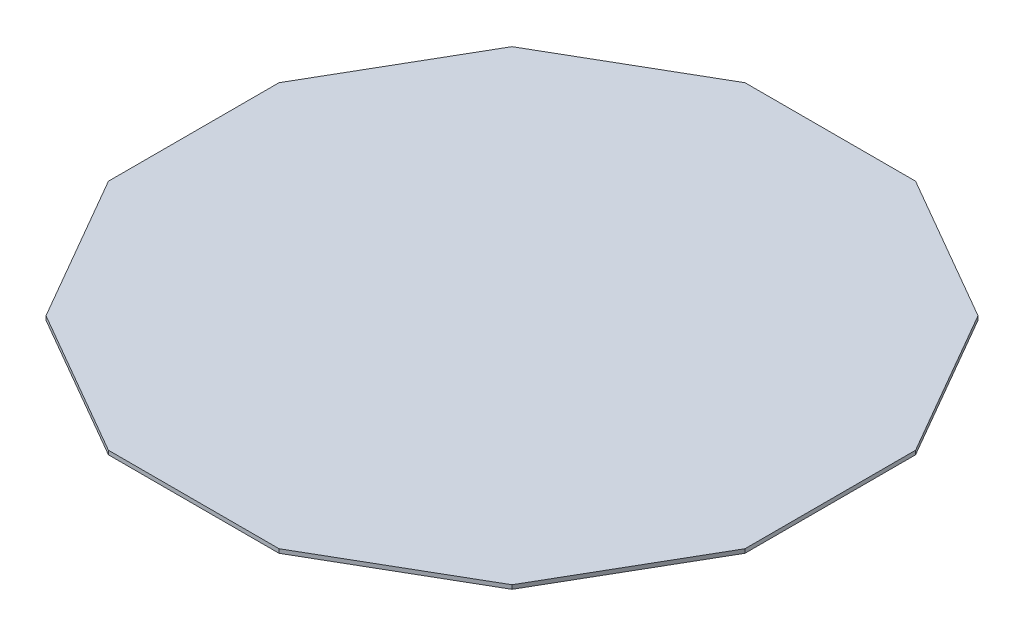
SolidWorks part; units mm, degrees
ref_plane "正面" through (0, 0, 0) normal (0, 0, 1) x (1, 0, 0)
ref_plane "平面" through (0, 0, 0) normal (0, 1, 0) x (1, 0, 0)
ref_plane "右側面" through (0, 0, 0) normal (1, 0, 0) x (0, 0, -1)
sketch "ｽｹｯﾁ1" plane through (0, 0, 0) normal (0, 1, 0) x (1, 0, 0)
  line L0 (-80, -21.4359) -> (-58.5641, -58.5641)
  line L1 (80, 21.4359) -> (58.5641, 58.5641)
  line L2 (58.5641, 58.5641) -> (21.4359, 80)
  line L3 (21.4359, 80) -> (-21.4359, 80)
  line L4 (-21.4359, 80) -> (-58.5641, 58.5641)
  line L5 (-58.5641, 58.5641) -> (-80, 21.4359)
  line L6 (-80, 21.4359) -> (-80, -21.4359)
  line L7 (-58.5641, -58.5641) -> (-21.4359, -80)
  line L8 (-21.4359, -80) -> (21.4359, -80)
  line L9 (21.4359, -80) -> (58.5641, -58.5641)
  line L10 (58.5641, -58.5641) -> (80, -21.4359)
  line L11 (80, -21.4359) -> (80, 21.4359)
  circle A0 centre (0, 0) radius 80 construction
extrude "ﾎﾞｽ - 押し出し1" add sketch "ｽｹｯﾁ1" along normal blind 1
